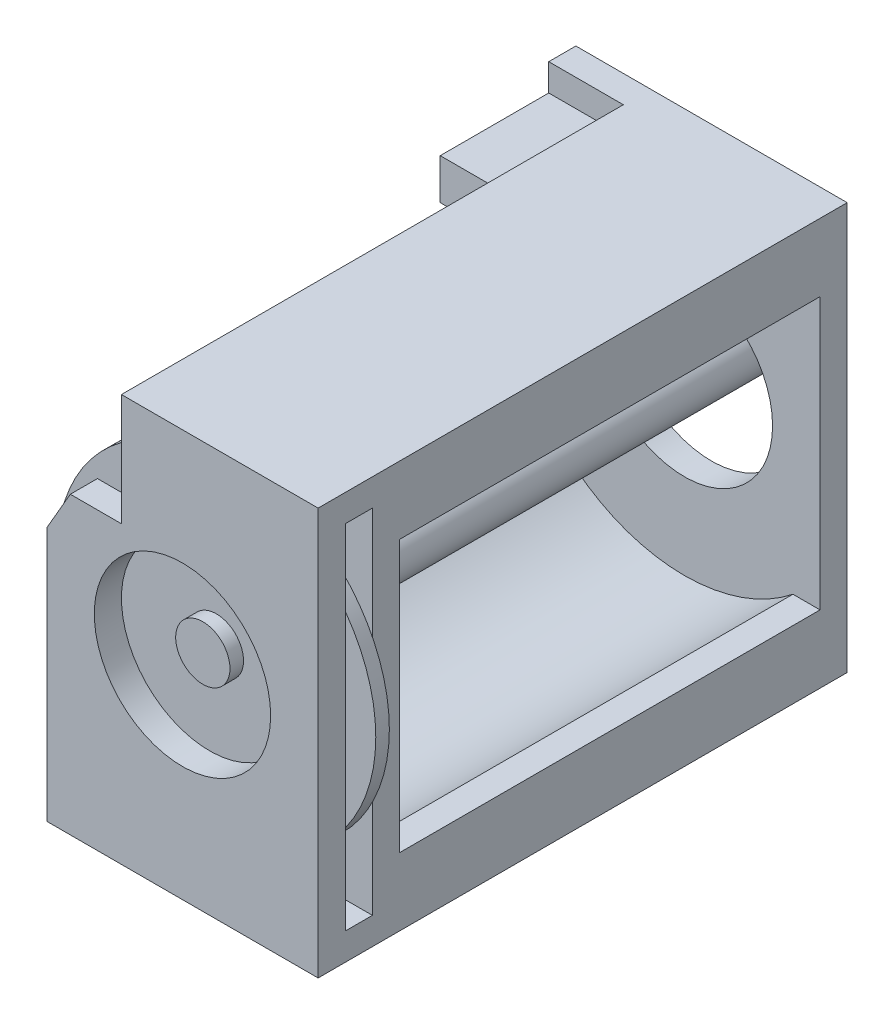
SolidWorks part; units mm, degrees
ref_plane "Front Plane" through (0, 0, 0) normal (0, 0, 1) x (1, 0, 0)
ref_plane "Top Plane" through (0, 0, 0) normal (0, 1, 0) x (1, 0, 0)
ref_plane "Right Plane" through (0, 0, 0) normal (1, 0, 0) x (0, 0, -1)
sketch "Sketch1" plane through (0, 0, 0) normal (0, 0, 1) x (1, 0, 0)
  line L0 (-10, 13) -> (10, 13) construction
  line L1 (10, 15) -> (-10, 15)
  line L2 (10, 15) -> (10, -15)
  line L3 (10, -15) -> (-10, -15)
  line L4 (-10, 15) -> (-10, -15)
  line L5 (10, 15) -> (-10, -15) construction
  line L6 (10, -15) -> (-10, 15) construction
  line L7 (-10, -13) -> (10, -13) construction
  line L8 (-8, 15) -> (-8, -15) construction
  line L9 (8, 15) -> (8, -15) construction
  line L10 (-10, 10) -> (-8, 10)
  line L11 (8, 10) -> (10, 10)
  line L12 (-10, -10) -> (-8, -10)
  line L13 (8, -10) -> (10, -10)
  line L14 (-8, 10) -> (-8, 13)
  line L15 (-8, 13) -> (8, 13)
  line L16 (8, 13) -> (8, 10)
  line L17 (8, -10) -> (8, -13)
  line L18 (8, -13) -> (-8, -13)
  line L19 (-8, -13) -> (-8, -10)
  line L20 (-8, 13) -> (-10, 13)
  line L21 (8, 13) -> (10, 13)
  line L22 (-8, -13) -> (-10, -13)
  line L23 (8, -13) -> (10, -13)
  circle A0 centre (0, 0) radius 6.5
  circle A1 centre (0, 0) radius 11.75 construction
  arc A2 (-8, 10) -> (8, 10) centre (0, 0) cw
  arc A3 (8, -10) -> (-8, -10) centre (0, 0) cw
  dimension "D1" = 13
  dimension "D3" = 23.5
  dimension "D2" = 30
  dimension "D4" = 20
  dimension "D5" = 2
  dimension "D6" = 2
  dimension "D7" = 2
  dimension "D8" = 2
  dimension "D9" = 3
  dimension "D10" = 3
extrude "Boss-Extrude1" add sketch "Sketch1" along normal blind 2 contours L15 L16 L11 L2 L1 L4 L10 L14 | L19 L18 L17 L13 L2 L11 L16 L15 L14 L10 L4 L12 A0 | L18 L19 L12 L4 L3 L2 L13 L17 | L2 L11 L16 L15 L14 L10 L4 | L2 L4 L12 L19 L18 L17 L13 | L14 L16 L15 | L14 L20 L4 L10 | L21 L16 L11 L2 | L17 L23 L2 L13 | L22 L19 L12 L4 region at (0, 14, 0) region at (9, 11.5, 0) region at (-9, 11.5, 0) region at (9.675, 0, 0) region at (7.8372, 11.5, 0) region at (9, -11.5, 0) region at (-9, -11.5, 0) region at (0, -14, 0) region at (7.8372, -11.5, 0)
extrude "Boss-Extrude4" add sketch "Sketch1<7>" along normal blind 34 contours L17 A3 L19 L18 | L18 L19 L12 L4 L3 L2 L13 L17 | L14 A2 L16 L15 | L15 L16 L11 L2 L1 L4 L10 L14 | L14 L20 L4 L10 | L21 L16 L11 L2 | L17 L23 L2 L13 | L22 L19 L12 L4 region at (0, 14, 0) region at (9, 11.5, 0) region at (-9, 11.5, 0) region at (7.8372, 11.5, 0) region at (9, -11.5, 0) region at (-9, -11.5, 0) region at (0, -14, 0) region at (7.8372, -11.5, 0)
sketch "Sketch1<7>" plane through (0, 0, 0) normal (0, 0, 1) x (1, 0, 0) same geometry as "Sketch1"
extrude "Boss-Extrude5" add sketch "Sketch1<9>" along normal blind 2 from offset 37 contours L14 A2 L16 L15 | L15 L16 L11 L2 L1 L4 L10 L14 | A3 L13 L2 L11 A2 L10 L4 L12 A0 | L17 A3 L19 L18 | L18 L19 L12 L4 L3 L2 L13 L17 | L14 L20 L4 L10 | L21 L16 L11 L2 | L17 L23 L2 L13 | L22 L19 L12 L4 region at (0, 14, 0) region at (9, 11.5, 0) region at (-9, 11.5, 0) region at (9.675, 0, 0) region at (7.8372, 11.5, 0) region at (9, -11.5, 0) region at (-9, -11.5, 0) region at (0, -14, 0) region at (7.8372, -11.5, 0)
sketch "Sketch1<9>" plane through (0, 0, 0) normal (0, 0, 1) x (1, 0, 0) same geometry as "Sketch1"
extrude "Boss-Extrude6" add sketch "Sketch1<10>" along normal blind 2 from offset 33 contours A3 L13 L2 L11 A2 L10 L4 L12 A0 | L17 A3 L19 L18 | L18 L19 L12 L4 L3 L2 L13 L17 | L14 A2 L16 L15 | L15 L16 L11 L2 L1 L4 L10 L14 | L14 L20 L4 L10 | L21 L16 L11 L2 | L17 L23 L2 L13 | L22 L19 L12 L4 region at (0, 14, 0) region at (9, 11.5, 0) region at (-9, 11.5, 0) region at (9.675, 0, 0) region at (7.8372, 11.5, 0) region at (9, -11.5, 0) region at (-9, -11.5, 0) region at (0, -14, 0) region at (7.8372, -11.5, 0)
sketch "Sketch1<10>" plane through (0, 0, 0) normal (0, 0, 1) x (1, 0, 0) same geometry as "Sketch1"
extrude "Boss-Extrude7" add sketch "Sketch1<11>" along normal blind 39 contours L15 L21 L2 L1 L4 L20 | L23 L18 L22 L4 L3 L2 region at (0, 14, 0) region at (0, -14, 0)
sketch "Sketch1<11>" plane through (0, 0, 0) normal (0, 0, 1) x (1, 0, 0) same geometry as "Sketch1"
sketch "Sketch2" plane through (0, 0, 39) normal (0, 0, 1) x (1, 0, 0)
  line L1 (10, -15) -> (-10, 15) construction
  line L2 (-10, 15) -> (-4.5, 15)
  line L3 (-10, 15) -> (-10, 6.75)
  line L4 (-10, 6.75) -> (-4.5, 6.75)
  line L8 (-4.5, 15) -> (-4.5, 6.75)
  dimension "D1" = 5.5
extrude "Cut-Extrude1" cut sketch "Sketch2" against normal blind 37
extrude "Boss-Extrude10" add sketch "Sketch1<12>" along normal blind 10 contours L14 L20 L4 L10 | L14 A2 L16 L15 region at (-9, 11.5, 0) region at (7.8372, 11.5, 0)
sketch "Sketch1<12>" plane through (0, 0, 0) normal (0, 0, 1) x (1, 0, 0) same geometry as "Sketch1"
sketch "Sketch4" plane through (0, 0, 0) normal (0, 0, 1) x (1, 0, 0)
  circle A0 centre (0, 0) radius 11.75
  circle A1 centre (0, 0) radius 2
extrude "Boss-Extrude8" add sketch "Sketch4" along normal blind 1 from offset 35.5 separate body
extrude "Boss-Extrude9" add sketch "Sketch4<2>" along normal blind 37.5 and the other way blind 5 separate body contours A1 region at (0, 0, 0)
sketch "Sketch4<2>" plane through (0, 0, 0) normal (0, 0, 1) x (1, 0, 0) same geometry as "Sketch4"
chamfer "Chamfer3" distance 3 angle 30 2 edges at (-10, 6.75, 34) (-10, 6.75, 38) first distance on face at (-10, 1.6875, 19.75)
